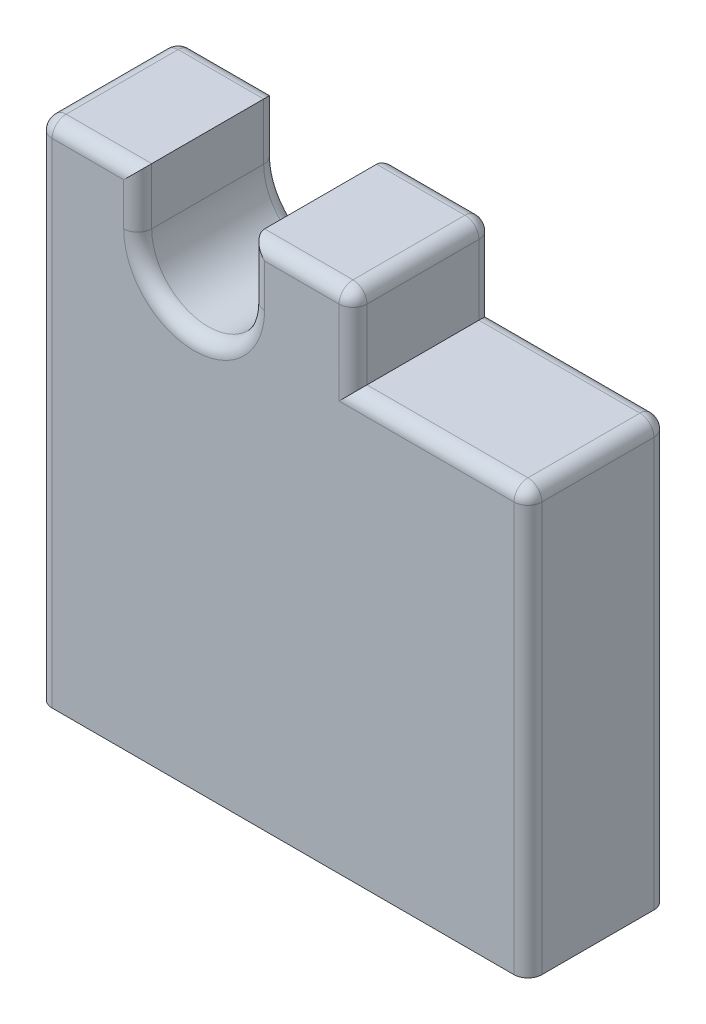
SolidWorks part; units mm, degrees
ref_plane "Front Plane" through (0, 0, 0) normal (0, 0, 1) x (1, 0, 0)
ref_plane "Top Plane" through (0, 0, 0) normal (0, 1, 0) x (1, 0, 0)
ref_plane "Right Plane" through (0, 0, 0) normal (1, 0, 0) x (0, 0, -1)
sketch "Sketch2" plane through (0, 0, 0) normal (0, 0, 1) x (1, 0, 0)
  line L0 (0, 0) -> (0, 92.075)
  line L1 (0, 92.075) -> (18.075, 92.075)
  line L2 (88.9, 76.835) -> (88.9, 0)
  line L3 (88.9, 0) -> (0, 0)
  line L4 (38.575, 92.075) -> (57.15, 92.075)
  line L6 (18.075, 92.075) -> (18.075, 81.825)
  line L7 (57.15, 92.075) -> (57.15, 76.835)
  line L8 (38.575, 81.825) -> (38.575, 92.075)
  line L9 (57.15, 76.835) -> (88.9, 76.835)
  arc A1 (18.075, 81.825) -> (38.575, 81.825) centre (28.325, 81.825) ccw
  point P10 (57.15, 92.075)
  dimension "D3" = 10.25
  dimension "D4" = 20.5
  dimension "D1" = 92.075
  dimension "D2" = 88.9
  dimension "D5" = 57.15
extrude "Boss-Extrude1" add sketch "Sketch2" along normal blind 25.4
fillet "Fillet4" radius 2.54 19 edges at (38.575, 86.95, 25.4) (18.075, 86.95, 25.4) (88.9, 38.4175, 25.4) (57.15, 84.455, 25.4) (73.025, 76.835, 25.4) (88.9, 76.835, 12.7) (47.8625, 92.075, 25.4) (28.325, 71.575, 25.4) (9.0375, 92.075, 25.4) (0, 46.0375, 25.4) (9.0375, 92.075, 0) (47.8625, 92.075, 0) (0, 46.0375, 0) (88.9, 38.4175, 0) (57.15, 84.455, 0) (73.025, 76.835, 0) (38.575, 86.95, 0) (18.075, 86.95, 0) (28.325, 71.575, 0)
fillet "Fillet5" radius 2.54 6 edges at (56.4061, 91.3311, 24.6561) (0.7439, 91.3311, 24.6561) (57.15, 92.075, 12.7) (0, 92.075, 12.7) (56.4061, 91.3311, 0.7439) (0.7439, 91.3311, 0.7439)
